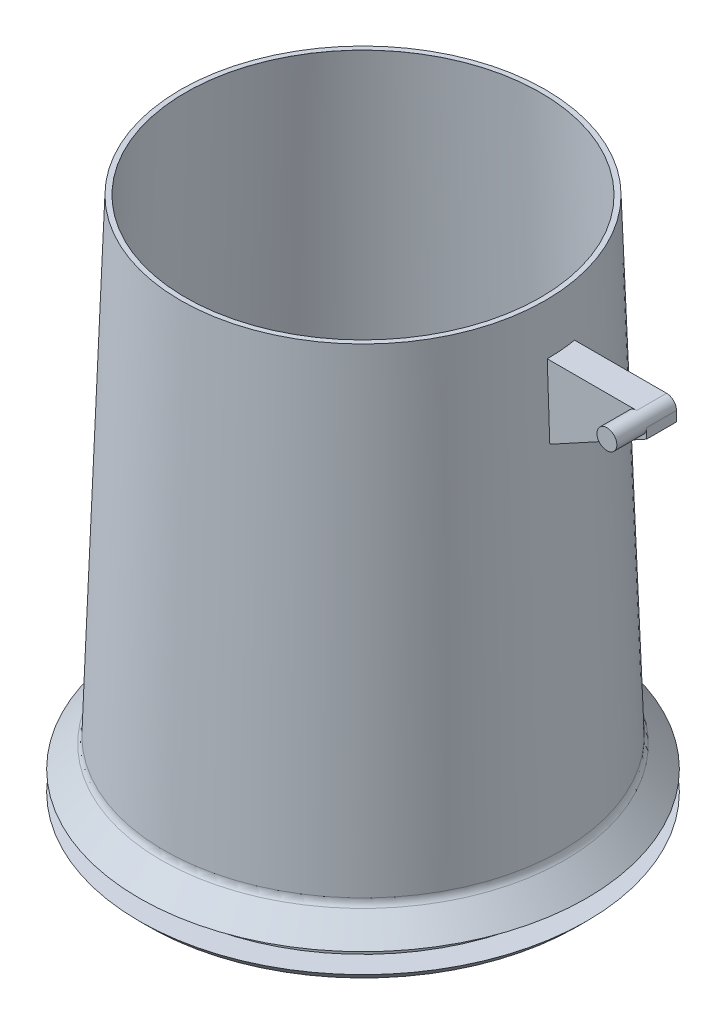
SolidWorks part; units mm, degrees
ref_plane "Front Plane" through (0, 0, 0) normal (0, 0, 1) x (1, 0, 0)
ref_plane "Top Plane" through (0, 0, 0) normal (0, 1, 0) x (1, 0, 0)
ref_plane "Right Plane" through (0, 0, 0) normal (1, 0, 0) x (0, 0, -1)
sketch "Sketch1" plane through (0, 0, 0) normal (0, 0, 1) x (1, 0, 0)
  line L0 (20, 0) -> (25, 0) construction
  line L1 (0, 0) -> (20, 0)
  line L2 (0, 0) -> (0, 50)
  line L3 (0, 50) -> (20, 50)
  line L4 (20, 2.9142) -> (20, 50)
  line L5 (22.5, 0) -> (20.2929, 2.2071)
  line L6 (20, 0) -> (22.5, 0)
  line L7 (20, 2.9142) -> (18.3557, 50)
  line L8 (19.5003, 2.8968) -> (17.856, 49.9826)
  line L15 (0.5, 49.5) -> (19.5, 49.5) construction
  line L16 (0.5, 0.5) -> (20, 0.5) construction
  line L17 (21.2929, 0.5) -> (19.9393, 1.8536) construction
  line L18 (20, 0.5) -> (21.2929, 0.5) construction
  line L19 (19.5, 2.9142) -> (19.5, 49.5) construction
  line L20 (19.5003, 2.8968) -> (19.6015, 0)
  line L21 (22.5, -2) -> (21.5, -3)
  line L22 (0.5, 0.5) -> (0.5, 49.5) construction
  line L23 (0, 0) -> (20, 0)
  line L24 (0, 0) -> (0, -2)
  line L25 (0, -2) -> (20, -2)
  line L26 (20, 0) -> (20, -2)
  line L27 (0, -2) -> (22.5, -2)
  line L28 (0, -2) -> (0, -3)
  line L29 (0, -3) -> (22.5, -3)
  line L30 (22.5, -2) -> (22.5, -3)
  line L31 (19.6015, 0) -> (19.7062, -3)
  line L32 (17.856, 49.9826) -> (17.856, 50)
  arc A0 (20.2929, 2.2071) -> (20, 2.9142) centre (21, 2.9142) cw
  arc A1 (19.5, 2.9046) -> (19.5, 2.9142) centre (21, 2.9142) cw
  arc A2 (19.9393, 1.8536) -> (19.5, 2.9142) centre (21, 2.9142) cw construction
  dimension "D1" = 1
  dimension "D2" = 20
  dimension "D3" = 2
  dimension "D5" = 20
  dimension "D6" = 2
  dimension "D7" = 22.5
  dimension "D8" = 1
  dimension "D4" = 0.5
revolve "Revolve1" add sketch "Sketch1" angle 360 about L2 region at (19.1807, 22.414, 0) region at (19.8176, -0.968, 0) region at (20.8624, -2.4627, 0)
sketch "Sketch2" plane through (0, 0, 0) normal (0, 0, 1) x (1, 0, 0)
  line L0 (18.7858, 37.6841) -> (28.5303, 43)
  line L1 (20, 2.9142) -> (18.3557, 50) construction
  line L2 (28.5303, 43) -> (28.5303, 45)
  line L3 (28.5303, 45) -> (18.5303, 45)
  line L4 (18.5303, 45) -> (18.2858, 45)
  line L5 (18.2858, 45) -> (18.2858, 37.6841)
  line L6 (18.2858, 37.6841) -> (18.7858, 37.6841)
  line L7 (18.3557, 50) -> (-18.3557, 50) construction
  circle A0 centre (27.5303, 44) radius 1
  dimension "D1" = 2
  dimension "D2" = 10
  dimension "D3" = 0.5
  dimension "D4" = 5
  dimension "D5" = 2
  dimension "D6" = 1
  dimension "D7" = 1
extrude "Boss-Extrude1" add sketch "Sketch2" against normal blind 3 contours A0 | L5 L6 L0 L2 L3 L4 A0 region at (22.0393, 42.2122, 0) region at (27.5303, 44, 0)
extrude "Boss-Extrude2" add sketch "Sketch2<3>" along normal blind 3 contours A0 region at (27.5303, 44, 0)
sketch "Sketch2<3>" plane through (0, 0, 0) normal (0, 0, 1) x (1, 0, 0) same geometry as "Sketch2"
